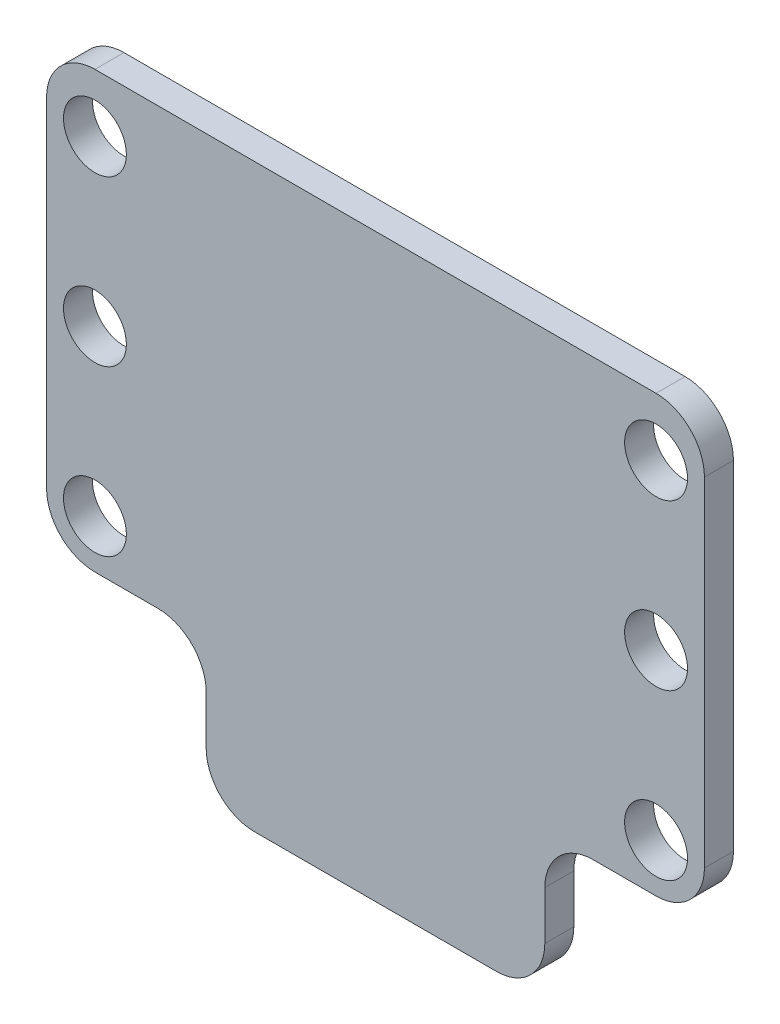
SolidWorks part; units mm, degrees
ref_plane "Plan de face" through (0, 0, 0) normal (0, 0, 1) x (1, 0, 0)
ref_plane "Plan de dessus" through (0, 0, 0) normal (0, 1, 0) x (1, 0, 0)
ref_plane "Plan de droite" through (0, 0, 0) normal (1, 0, 0) x (0, 0, -1)
sketch "Esquisse2" plane through (0, 0, 0) normal (0, 0, 1) x (1, 0, 0)
  line L0 (39.2085, -84.0985) -> (39.2085, -11.0985) construction
  line L1 (107.2085, -4.0985) -> (39.2085, -4.0985)
  line L2 (107.2085, -4.0985) -> (107.2085, -49.0985)
  line L3 (107.2085, -49.0985) -> (90.7085, -49.0985)
  line L4 (39.2085, -4.0985) -> (39.2085, -49.0985)
  line L5 (55.7085, -49.0985) -> (39.2085, -49.0985)
  line L7 (90.7085, -49.0985) -> (90.7085, -64.0985)
  line L8 (90.7085, -64.0985) -> (55.7085, -64.0985)
  line L9 (55.7085, -49.0985) -> (55.7085, -64.0985)
  circle A0 centre (102.2085, -10.0985) radius 3.25
  circle A1 centre (102.2085, -44.0985) radius 3.25
  circle A2 centre (44.2085, -44.0985) radius 3.25
  circle A3 centre (44.2085, -10.0985) radius 3.25
  circle A4 centre (44.2085, -27.0985) radius 3.25
  circle A5 centre (102.2085, -27.0985) radius 3.25
  point P23 (73.2085, -64.0985)
  point P24 (73.2085, -4.0985)
  dimension "D4" = 6.5
  dimension "D1" = 45
  dimension "D2" = 15
  dimension "D3" = 35
  dimension "D5" = 17
extrude "Boss.-Extru.1" add sketch "Esquisse2" along normal blind 3
fillet "Congé1" radius 5 8 edges at (39.2085, -4.0985, 1.5) (39.2085, -49.0985, 1.5) (55.7085, -64.0985, 1.5) (55.7085, -49.0985, 1.5) (90.7085, -64.0985, 1.5) (90.7085, -49.0985, 1.5) (107.2085, -49.0985, 1.5) (107.2085, -4.0985, 1.5)
